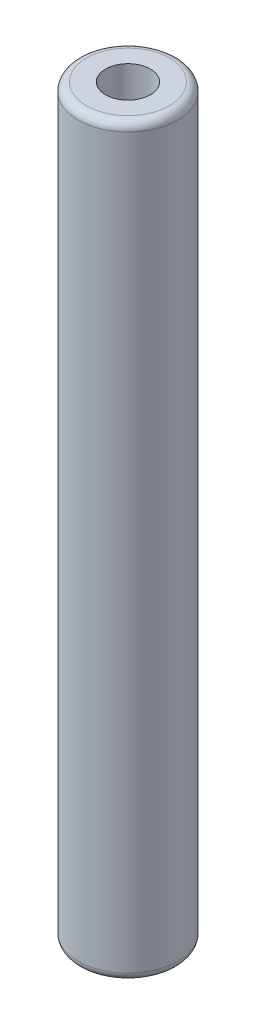
SolidWorks part; units mm, degrees
material "1060 Alloy"
ref_plane "Front Plane" through (0, 0, 0) normal (0, 0, 1) x (1, 0, 0)
ref_plane "Top Plane" through (0, 0, 0) normal (0, 1, 0) x (1, 0, 0)
ref_plane "Right Plane" through (0, 0, 0) normal (1, 0, 0) x (0, 0, -1)
sketch "Sketch1" plane through (0, 0, 0) normal (0, 1, 0) x (1, 0, 0)
  circle A0 centre (0, 0) radius 3
  dimension "D1" = 6
extrude "Boss-Extrude1" add sketch "Sketch1" along normal blind 22.5 and the other way blind 22.5
hole_wizard "#6-32 Tapped Hole1" positions "Sketch2" profile "Sketch3" tap size "#6-32" standard "ANSI Inch"
sketch "Sketch2" plane through (0, 22.5, 0) normal (0, 1, 0) x (1, 0, 0)
  point P0 (0, 0)
sketch "Sketch3" plane through (0, 22.5, 0) normal (1, 0, 0) x (0, 0, 1)
  line L0 (0, 0) -> (0, 11.1627)
  line L1 (0, 11.1627) -> (1.3525, 10.35)
  line L2 (1.3525, 10.35) -> (1.3525, 0)
  line L5 (1.3525, 0) -> (0, 0)
  line L10 (0, 11.1627) -> (-1.3525, 10.35) construction
  line L11 (0, -6.35) -> (0, 107.95) construction
  dimension "Tap Drill Dia." = 2.7051
  dimension "Tap Drill Depth" = 10.35
  dimension "Drill Angle" = 118
fillet "Fillet1" radius 0.5 2 edges at (0, 22.5, 3) (0, -22.5, 3)
hole_wizard "#6-32 Tapped Hole2" positions "Sketch4" profile "Sketch5" tap size "#6-32" standard "ANSI Inch"
sketch "Sketch4" plane through (0, -22.5, 0) normal (0, -1, 0) x (-1, 0, 0)
  point P0 (0, 0)
sketch "Sketch5" plane through (0, -22.5, 0) normal (1, 0, 0) x (0, 0, -1)
  line L0 (0, 0) -> (0, 11.1627)
  line L1 (0, 11.1627) -> (1.3525, 10.35)
  line L2 (1.3525, 10.35) -> (1.3525, 0)
  line L5 (1.3525, 0) -> (0, 0)
  line L10 (0, 11.1627) -> (-1.3525, 10.35) construction
  line L11 (0, -6.35) -> (0, 107.95) construction
  dimension "Tap Drill Dia." = 2.7051
  dimension "Tap Drill Depth" = 10.35
  dimension "Drill Angle" = 118
